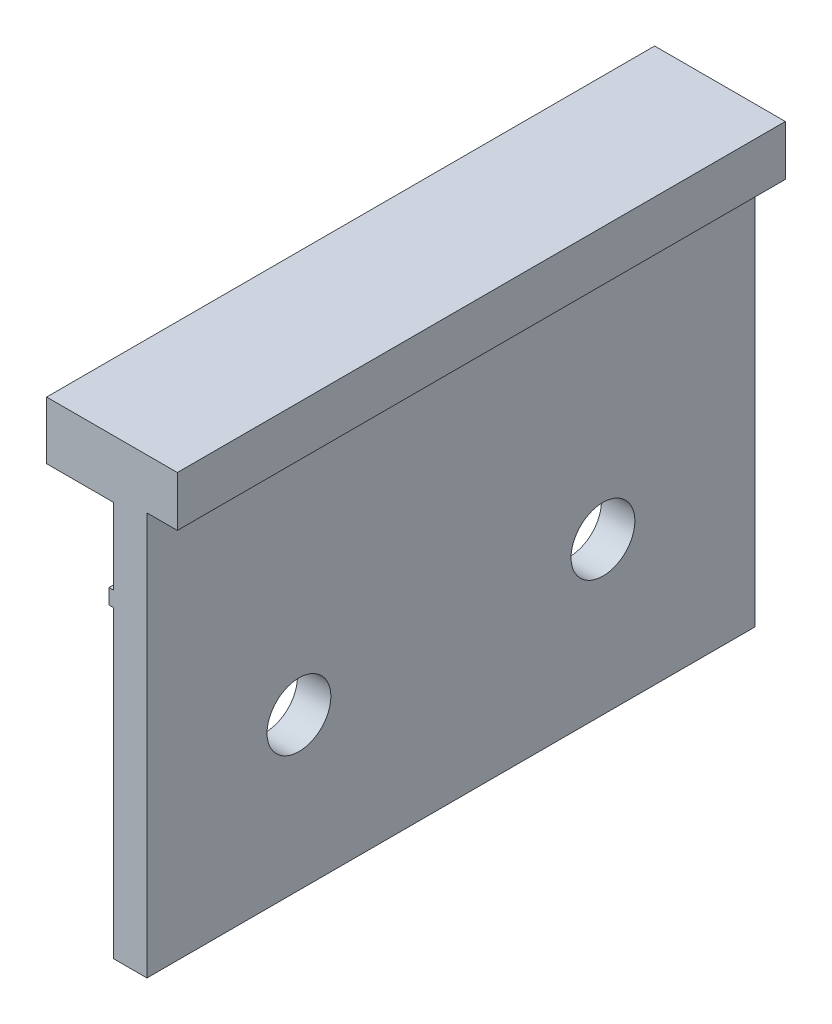
SolidWorks part; units mm, degrees
ref_plane "xy_plane" through (0, 0, 0) normal (0, 0, 1) x (1, 0, 0)
ref_plane "zx_plane" through (0, 0, 0) normal (0, 1, 0) x (1, 0, 0)
ref_plane "yz_plane" through (0, 0, 0) normal (1, 0, 0) x (0, 0, -1)
ref_plane "zMid_plane" through (0, 0, 0) normal (0, 0, 1) x (1, 0, 0)
ref_plane "zMin_plane" through (0, 0, -20) normal (0, 0, 1) x (1, 0, 0)
ref_plane "zMax_plane" through (0, 0, 20) normal (0, 0, 1) x (1, 0, 0)
ref_axis "x_axis" through (-80.9, 0, 0) along (1, 0, 0)
ref_axis "y_axis" through (0, -50, 0) along (0, 1, 0)
ref_axis "z_axis" through (0, 0, -80.9) along (0, 0, 1)
sketch "tSlotProfile_sketch" plane through (0, 0, 0) normal (0, 0, 1) x (1, 0, 0)
  line B0 (-4.0958, -2.8679) -> (-4.9968, -3.4988)
  line B1 (-28.5, -5.8) -> (-28.5, -5)
  line B2 (5.8, -30) -> (5.8, -28.5)
  line B3 (5.8, -28.5) -> (5, -28.5)
  line B4 (-5, -28.5) -> (-5.8, -28.5)
  line B5 (-5.8, -28.5) -> (-5.8, -30)
  line B6 (-30, -5.8) -> (-28.5, -5.8)
  line B7 (17.9899, -11.85) -> (11.85, -17.9899)
  line B8 (11.85, -17.9899) -> (11.85, -25.8)
  line B9 (11.85, -25.8) -> (7.5, -25.8)
  line B10 (7.5, -25.8) -> (7.5, -28.2)
  line B11 (7.5, -28.2) -> (25.7, -28.2)
  line B12 (28.2, -25.7) -> (28.2, -7.5)
  line B13 (25.8, -7.5) -> (25.8, -11.85)
  line B14 (25.8, -11.85) -> (17.9899, -11.85)
  line B15 (28.2, 7.5) -> (28.2, 25.7)
  line B16 (-11.85, -17.9899) -> (-17.9899, -11.85)
  line B17 (-17.9899, -11.85) -> (-25.8, -11.85)
  line B18 (-28.2, -7.5) -> (-28.2, -25.7)
  line B19 (-25.7, -28.2) -> (-7.5, -28.2)
  line B20 (-7.5, -28.2) -> (-7.5, -25.8)
  line B21 (-7.5, -25.8) -> (-11.85, -25.8)
  line B22 (-11.85, -25.8) -> (-11.85, -17.9899)
  line B23 (0.9, -15.2) -> (7.9956, -15.2)
  line B24 (7.9956, -15.2) -> (10.045, -17.2494)
  line B25 (10.045, -17.2494) -> (17.2494, -10.045)
  line B26 (15.2, -0.9) -> (7.9995, -0.9)
  line B27 (0.9, -7.9995) -> (0.9, -15.2)
  line B28 (17.2494, 10.045) -> (10.045, 17.2494)
  line B29 (0.9, 15.2) -> (0.9, 7.9995)
  line B30 (7.9995, 0.9) -> (15.2, 0.9)
  line B31 (-15.2, 0.9) -> (-7.9995, 0.9)
  line B32 (-15.2, -0.9) -> (-15.2, -7.9956)
  line B33 (-17.2494, -10.045) -> (-10.045, -17.2494)
  line B34 (-10.045, -17.2494) -> (-7.9956, -15.2)
  line B35 (-7.9956, -15.2) -> (-0.9, -15.2)
  line B36 (-0.9, -15.2) -> (-0.9, -7.9995)
  line B37 (-7.9995, -0.9) -> (-15.2, -0.9)
  line B38 (-28.5, -5) -> (-24, -5)
  line B39 (-24, -10.05) -> (-19.8, -10.05)
  line B40 (-24, 5) -> (-28.5, 5)
  line B41 (-30, 5.8) -> (-30, 27)
  line B42 (-27, 30) -> (-5.8, 30)
  line B43 (17, 7.25) -> (17, -7.25)
  line B44 (19.8, -10.05) -> (24, -10.05)
  line B45 (24, -5) -> (28.5, -5)
  line B46 (30, -5.8) -> (30, -27)
  line B47 (27, -30) -> (5.8, -30)
  line B48 (5, -28.5) -> (5, -24)
  line B49 (5, -24) -> (10.05, -24)
  line B50 (10.05, -24) -> (10.05, -19.8)
  line B51 (10.05, -19.8) -> (7.25, -17)
  line B52 (7.25, -17) -> (-7.25, -17)
  line B53 (-7.25, -17) -> (-10.05, -19.8)
  line B54 (-10.05, -19.8) -> (-10.05, -24)
  line B55 (-10.05, -24) -> (-5, -24)
  line B56 (-5, -24) -> (-5, -28.5)
  line B57 (-5.8, -30) -> (-27, -30)
  line B58 (-30, -27) -> (-30, -5.8)
  line B59 (30, 27) -> (30, 5.8)
  arc B60 (25.7, -28.2) -> (28.2, -25.7) centre (25.7, -25.7) ccw
  arc B61 (-28.2, -25.7) -> (-25.7, -28.2) centre (-25.7, -25.7) ccw
  arc B62 (0.9, -7.9995) -> (7.9995, -0.9) centre (0, 0) ccw
  arc B63 (-0.9, 7.9995) -> (-7.9995, 0.9) centre (0, 0) ccw
  arc B64 (-7.9995, -0.9) -> (-0.9, -7.9995) centre (0, 0) ccw
  arc B65 (-4.9968, 3.4988) -> (-6.0073, 1.0593) centre (0, 0) ccw
  arc B66 (27, -30) -> (30, -27) centre (27, -27) ccw
  arc B67 (-30, -27) -> (-27, -30) centre (-27, -27) ccw
sketch_block_instance "rexroth_60x60L-1"
sketch_block "Block1"
ref_plane "beam YMin_plane" through (0, -30, 0) normal (0, 1, 0) x (1, 0, 0)
sketch "panelClipSection_sketch" plane through (0, 0, 0) normal (0, 0, 1) x (1, 0, 0)
  line L0 (-9.4, -24) -> (-5, -24)
  line L1 (-5, -24) -> (-5, -50)
  line L2 (-5, -50) -> (-2.8, -50)
  line L3 (-2.8, -50) -> (-2.8, -23.5)
  line L4 (-2.8, -23.5) -> (-0.8, -23.5)
  line L5 (-0.8, -23.5) -> (-0.8, -20.2)
  line L6 (-0.8, -20.2) -> (-9.4, -20.2)
  line L7 (-9.4, -20.2) -> (-9.4, -24)
  line L9 (0, -50) -> (0, 50) construction
  line L10 (-80.9, 0) -> (80.9, 0) construction
  dimension "d" = 3.8
  dimension "c" = 2
  dimension "b" = 2.2
  dimension "f" = 3.3
  dimension "a" = 4.4
  dimension "e" = 26
extrude "clip_extrude" add sketch "panelClipSection_sketch" along normal up to surface (20 mm away) from surface up to plane "zMax_plane" starting at plane "zMin_plane"
sketch "antiUpliftBump_sketch" plane through (0, 0, 0) normal (0, 0, 1) x (1, 0, 0)
  line L0 (-5, -24) -> (-5, -50) construction
  line L1 (-5.3, -29) -> (-5, -29)
  line L2 (-5.3, -29) -> (-5.3, -30)
  line L3 (-5.3, -30) -> (-5, -30)
  line L4 (-5, -29) -> (-5, -30)
  line L5 (-5.8, -30) -> (-27, -30) construction
  line L6 (-5, -28.5) -> (-5.8, -28.5) construction
  line L7 (-5.8, -28.5) -> (-5.8, -30) construction
  dimension "D1" = 0.5
  dimension "D2" = 0.5
extrude "antiOffsetBump_extrude" add sketch "antiUpliftBump_sketch" along normal up to surface (20 mm away) from surface up to plane "zMax_plane" starting at plane "zMin_plane"
sketch "mountHoles_sketch" plane through (0, 0, 0) normal (1, 0, 0) x (0, 0, -1)
  line L0 (10, -40) -> (-10, -40) construction
  line L1 (80.9, 0) -> (-80.9, 0) construction
  line L2 (0, 55) -> (0, -55) construction
  line L3 (50, -30) -> (-50, -30) construction
  circle A0 centre (10, -40) radius 2.1
  circle A1 centre (-10, -40) radius 2.1
  dimension "D3" = 4.2
  dimension "D2" = 20
  dimension "D4" = 10
  dimension "D5" = 10
extrude "mountHoles_cut" cut sketch "mountHoles_sketch" against normal through all both and the other way through all
equation "\"D1@zMin_plane\"=\"externalParameters.this.extentZ\"/2"
equation "\"D1@zMax_plane\"=\"externalParameters.this.extentZ\"/2"
equation "\"a@panelClipSection_sketch\"=\"externalParameters.this.a\""
equation "\"b@panelClipSection_sketch\"=\"externalParameters.this.b\""
equation "\"c@panelClipSection_sketch\"=\"externalParameters.this.c\""
equation "\"d@panelClipSection_sketch\"=\"externalParameters.this.d\""
equation "\"e@panelClipSection_sketch\"=\"externalParameters.this.e\""
equation "\"f@panelClipSection_sketch\"=\"externalParameters.this.f\""
equation "\"D5@mountHoles_sketch\"=\"externalParameters.this.mountHoles.offsetYFromBeam\""
equation "\"D3@mountHoles_sketch\"=\"externalParameters.this.mountHoles.diameter\""
equation "\"D4@mountHoles_sketch\"=\"externalParameters.this.mountHoles.spanZ\"/2"
equation "\"D1@mountHoles_sketch\"=\"externalParameters.this.mountHoles.count\""
equation "\"D2@mountHoles_sketch\"= \"externalParameters.this.mountHoles.intervalZ\""
equation "\"D1@antiUpliftBump_sketch\" = 0.5mm"
equation "\"D2@antiUpliftBump_sketch\" = 0.5mm"
